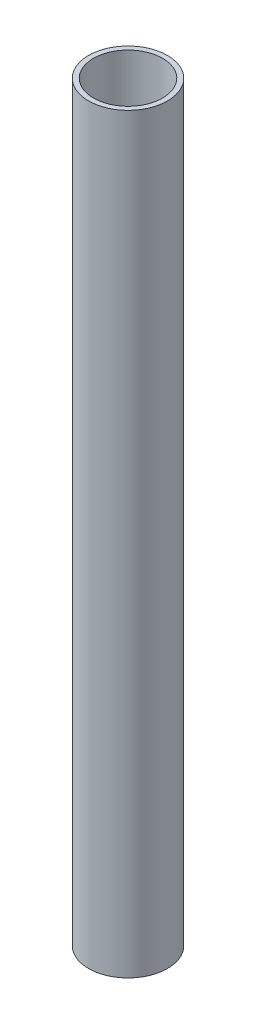
SolidWorks part; units mm, degrees
ref_plane "Front Plane" through (0, 0, 0) normal (0, 0, 1) x (1, 0, 0)
ref_plane "Top Plane" through (0, 0, 0) normal (0, 1, 0) x (1, 0, 0)
ref_plane "Right Plane" through (0, 0, 0) normal (1, 0, 0) x (0, 0, -1)
sketch "Sketch1" plane through (0, 0, 0) normal (0, 1, 0) x (1, 0, 0)
  circle A0 centre (0, 0) radius 3.5
  circle A1 centre (0, 0) radius 4
  dimension "D1" = 7
  dimension "D2" = 8
extrude "Boss-Extrude1" add sketch "Sketch1" along normal blind 76.2
